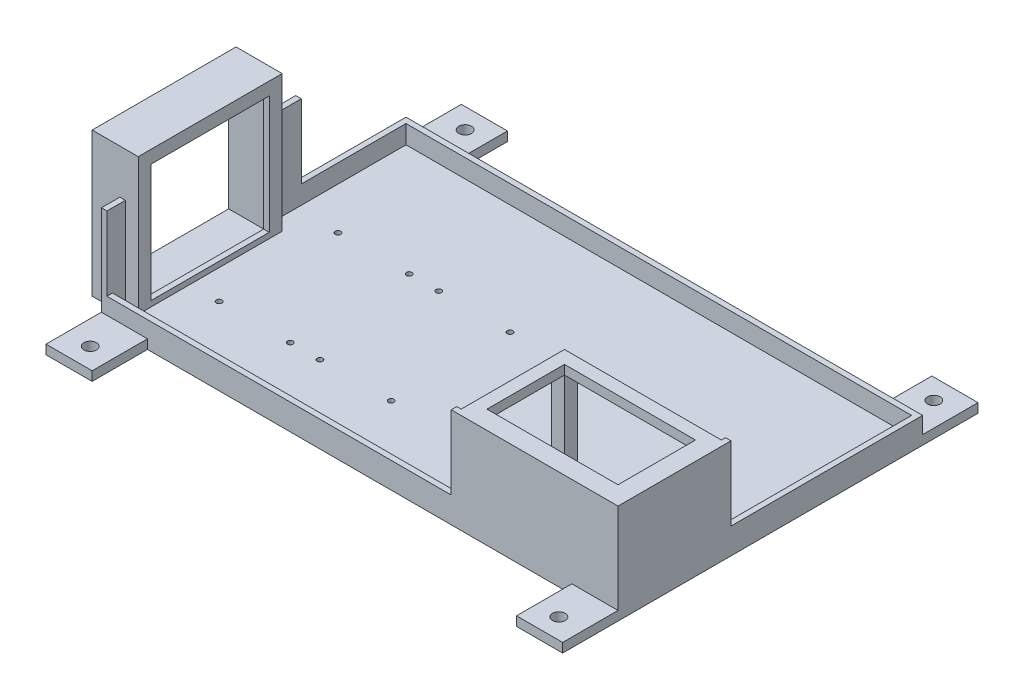
SolidWorks part; units mm, degrees
ref_plane "Front Plane" through (0, 0, 0) normal (0, 0, 1) x (1, 0, 0)
ref_plane "Top Plane" through (0, 0, 0) normal (0, 1, 0) x (1, 0, 0)
ref_plane "Right Plane" through (0, 0, 0) normal (1, 0, 0) x (0, 0, -1)
sketch "Sketch1" plane through (0, 0, 0) normal (0, 1, 0) x (1, 0, 0)
  line L1 (-140, -82.55) -> (140, -82.55)
  line L2 (-140, -82.55) -> (-140, 82.55)
  line L3 (-140, 82.55) -> (140, 82.55)
  line L4 (140, -82.55) -> (140, 82.55)
  line L5 (-140, -82.55) -> (140, 82.55) construction
  line L6 (-140, 82.55) -> (140, -82.55) construction
  point P0 (0, 0)
  dimension "D1" = 165.1
  dimension "D2" = 280
extrude "Floor" add sketch "Sketch1" along normal blind 4
sketch "Sketch2" plane through (0, 4, 0) normal (0, 1, 0) x (1, 0, 0)
  line L0 (137, -79.55) -> (137, 79.55)
  line L1 (137, 79.55) -> (-137, 79.55)
  line L2 (-137, 79.55) -> (-137, -79.55)
  line L3 (-137, -79.55) -> (137, -79.55)
  line L4 (140, -82.55) -> (140, 82.55)
  line L5 (140, 82.55) -> (-140, 82.55)
  line L6 (-140, 82.55) -> (-140, -82.55)
  line L7 (-140, -82.55) -> (140, -82.55)
  line L8 (140, -82.55) -> (140, 82.55)
  line L9 (140, 82.55) -> (-140, 82.55)
  line L10 (-140, 82.55) -> (-140, -82.55)
  line L11 (-140, -82.55) -> (140, -82.55)
  dimension "D1" = 0
  dimension "D2" = 3
extrude "Wall" add sketch "Sketch2" along normal blind 10
sketch "Sketch4" plane through (0, 4, 0) normal (0, 1, 0) x (1, 0, 0)
  line L0 (130, -30.55) -> (59, -30.55)
  line L1 (137, -79.55) -> (52, -79.55)
  line L2 (137, -79.55) -> (137, -23.55)
  line L3 (137, -23.55) -> (52, -23.55)
  line L4 (52, -79.55) -> (52, -23.55)
  line L5 (59, -72.55) -> (59, -30.55)
  line L6 (130, -72.55) -> (59, -72.55)
  line L7 (130, -72.55) -> (130, -30.55)
  dimension "D1" = 85
  dimension "D2" = 56
  dimension "D3" = 7
extrude "Rpi stand" add sketch "Sketch4" along normal blind 5 from offset 45
sketch "Sketch7" plane through (0, 14, 0) normal (0, 1, 0) x (1, 0, 0)
  line L0 (-137, 79.55) -> (-137, -79.55) construction
  line L1 (-140, -82.55) -> (-137, -82.55)
  line L2 (-140, -82.55) -> (-140, 22.7839)
  line L3 (-140, 22.7839) -> (-137, 22.7839)
  line L4 (-137, -82.55) -> (-137, 22.7839)
  line L5 (-137, -79.55) -> (137, -79.55) construction
  line L6 (140, -82.55) -> (49.6123, -82.55)
  line L7 (140, -82.55) -> (140, -79.55)
  line L8 (137, -79.55) -> (49.6123, -79.55)
  line L9 (49.6123, -82.55) -> (49.6123, -79.55)
  line L10 (137, -79.55) -> (137, 79.55) construction
  line L12 (140, -79.55) -> (140, -21.3069)
  line L13 (140, -21.3069) -> (137, -21.3069)
  line L14 (137, -79.55) -> (137, -21.3069)
  line L15 (-137, -79.55) -> (137, -79.55) construction
extrude "Temp support" add sketch "Sketch7" along normal blind 40
sketch "Sketch3" plane through (0, 0, 0) normal (0, 1, 0) x (1, 0, 0)
  line L0 (-127, 101.6) -> (127, 101.6) construction
  line L1 (-140, 82.55) -> (-115, 82.55)
  line L2 (-140, 82.55) -> (-140, 112.55)
  line L3 (-140, 112.55) -> (-115, 112.55)
  line L4 (-115, 82.55) -> (-115, 112.55)
  line L5 (140, 82.55) -> (115, 82.55)
  line L6 (140, 82.55) -> (140, 112.55)
  line L7 (140, 112.55) -> (115, 112.55)
  line L8 (115, 82.55) -> (115, 112.55)
  line L9 (-140, -82.55) -> (-115, -82.55)
  line L10 (-140, -82.55) -> (-140, -112.55)
  line L11 (-140, -112.55) -> (-115, -112.55)
  line L12 (-115, -82.55) -> (-115, -112.55)
  line L13 (140, -82.55) -> (115, -82.55)
  line L14 (140, -82.55) -> (140, -112.55)
  line L15 (140, -112.55) -> (115, -112.55)
  line L16 (115, -82.55) -> (115, -112.55)
  line L17 (127, 101.6) -> (127, -101.6) construction
  line L18 (127, -101.6) -> (-127, -101.6) construction
  line L19 (-127, -101.6) -> (-127, 101.6) construction
  line L20 (-140, 30.6215) -> (140, 30.6215) construction
  line L22 (140, -21.3069) -> (140, 82.55) construction
  line L23 (0, 101.6) -> (0, -101.6) construction
  line L24 (-140, 22.7839) -> (-140, -82.55) construction
  line L25 (140, -21.3069) -> (140, 82.55) construction
  line L26 (-137, -82.55) -> (49.6123, -82.55) construction
  circle A0 centre (-127, 101.6) radius 3.429
  circle A1 centre (127, 101.6) radius 3.429
  circle A2 centre (127, -101.6) radius 3.429
  circle A3 centre (-127, -101.6) radius 3.429
  point P28 (-127.5, -82.55)
  point P29 (-115, -97.55)
  point P30 (127.5, -82.55)
  point P31 (-115, 97.55)
  dimension "D5" = 6.858
  dimension "D1" = 25
  dimension "D2" = 25
  dimension "D3" = 30
  dimension "D4" = 30
  dimension "D6" = 203.2
  dimension "D7" = 254
extrude "Brackets" add sketch "Sketch3" along normal blind 5
sketch "Sketch5" plane through (-140, 0, 0) normal (-1, 0, 0) x (0, 0, 1)
  line L0 (-5.45, 78) -> (72.55, 78)
  line L1 (-1.45, 4) -> (68.55, 4)
  line L2 (-1.45, 4) -> (-1.45, 74)
  line L3 (-1.45, 74) -> (68.55, 74)
  line L4 (68.55, 4) -> (68.55, 74)
  line L5 (72.55, 0) -> (72.55, 78)
  line L6 (-5.45, 0) -> (72.55, 0)
  line L7 (-5.45, 0) -> (-5.45, 78)
  line L9 (112.55, 5) -> (112.55, 0) construction
  line L11 (-79.55, 4) -> (79.55, 4) construction
  dimension "D1" = 70
  dimension "D2" = 70
  dimension "D5" = 40
  dimension "D3" = 4
extrude "Fan Holder" add sketch "Sketch5" along normal blind 15 and the other way blind 10
sketch "Sketch8" plane through (-140, 0, 0) normal (-1, 0, 0) x (0, 0, 1)
  line L4 (-1.45, 54) -> (-1.45, 4)
  line L5 (-1.45, 4) -> (68.55, 4)
  line L6 (68.55, 4) -> (68.55, 54)
  line L7 (68.55, 54) -> (-1.45, 54)
  line L8 (-1.45, 54) -> (-1.45, 4)
  line L9 (-1.45, 4) -> (68.55, 4)
  line L10 (68.55, 4) -> (68.55, 54)
  line L15 (68.55, 54) -> (-1.45, 54)
  dimension "D1" = 0
extrude "Fan hole" cut sketch "Sketch8" against normal up to next (3 mm away)
sketch "Sketch11" plane through (-130, 0, 0) normal (-1, 0, 0) x (0, 0, 1)
  line L4 (-5.45, 78) -> (-5.45, 0)
  line L5 (-5.45, 0) -> (72.55, 0)
  line L6 (72.55, 0) -> (72.55, 78)
  line L7 (72.55, 78) -> (-5.45, 78)
  line L8 (-5.45, 78) -> (-5.45, 0)
  line L9 (-5.45, 0) -> (72.55, 0)
  line L10 (72.55, 0) -> (72.55, 78)
  line L11 (72.55, 78) -> (-5.45, 78)
  line L16 (1.55, 71) -> (1.55, 7)
  line L17 (1.55, 7) -> (65.55, 7)
  line L18 (65.55, 7) -> (65.55, 71)
  line L19 (65.55, 71) -> (1.55, 71)
  line L20 (1.55, 71) -> (1.55, 7)
  line L21 (1.55, 7) -> (65.55, 7)
  line L22 (65.55, 7) -> (65.55, 71)
  line L23 (65.55, 71) -> (1.55, 71)
  dimension "D1" = 0
  dimension "D2" = 7
extrude "Boss-Extrude9" add sketch "Sketch11" along normal blind 3
sketch "Sketch12" plane through (0, 49, 0) normal (0, -1, 0) x (1, 0, 0)
  line L1 (52, 23.55) -> (59, 23.55)
  line L2 (52, 23.55) -> (52, 30.55)
  line L3 (52, 30.55) -> (59, 30.55)
  line L4 (59, 23.55) -> (59, 30.55)
  dimension "D1" = 7
  dimension "D2" = 7
extrude "Boss-Extrude10" add sketch "Sketch12" along normal up to next
sketch "Sketch13" plane through (0, 4, 0) normal (0, 1, 0) x (1, 0, 0)
  line L0 (-137, 79.55) -> (-137, 5.45) construction
  line L1 (137, 79.55) -> (-137, 79.55) construction
  line L2 (-114.12, 19.79) -> (-75.52, 19.79) construction
  line L3 (-75.52, 19.79) -> (-75.52, -44.61) construction
  line L4 (-75.52, 19.79) -> (-59.48, 19.79) construction
  line L5 (-59.48, 19.79) -> (-59.48, -44.61) construction
  line L6 (-75.52, -44.61) -> (-59.48, -44.61) construction
  line L7 (-59.48, 19.79) -> (-20.88, 19.79) construction
  line L8 (-20.88, 19.79) -> (-20.88, -44.61) construction
  line L9 (-59.48, -44.61) -> (-20.88, -44.61) construction
  circle A0 centre (-114.12, 19.79) radius 1.5
  circle A1 centre (-114.12, -44.61) radius 1.5
  circle A2 centre (-75.52, 19.79) radius 1.5
  circle A3 centre (-75.52, -44.61) radius 1.5
  circle A4 centre (-59.48, 19.79) radius 1.5
  circle A5 centre (-59.48, -44.61) radius 1.5
  circle A6 centre (-20.88, 19.79) radius 1.5
  circle A7 centre (-20.88, -44.61) radius 1.5
  dimension "D1" = 22.88
  dimension "D2" = 59.76
  dimension "D3" = 3
  dimension "D4" = 3
  dimension "D5" = 64.4
  dimension "D6" = 22.88
  dimension "D7" = 3
  dimension "D8" = 3
  dimension "D12" = 3
  dimension "D13" = 3
  dimension "D15" = 3
  dimension "D16" = 3
  dimension "D9" = 64.4
  dimension "D10" = 38.6
  dimension "D11" = 16.04
  dimension "D14" = 38.6
extrude "Cut-Extrude1" cut sketch "Sketch13" against normal through all
equation "\"D2@Sketch3\"=\"D1@Sketch3\""
equation "\"D4@Sketch3\"=\"D3@Sketch3\""
